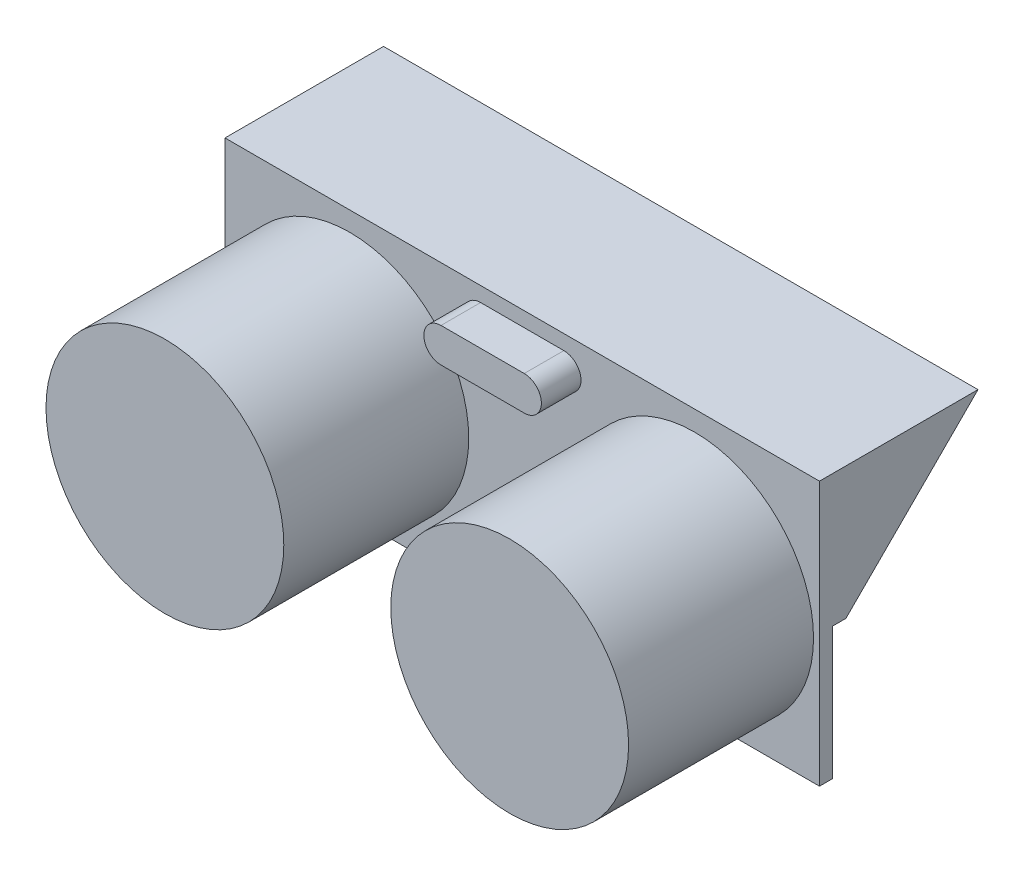
SolidWorks part; units mm, degrees
ref_plane "Plan de face" through (0, 0, 0) normal (0, 0, 1) x (1, 0, 0)
ref_plane "Plan de dessus" through (0, 0, 0) normal (0, 1, 0) x (1, 0, 0)
ref_plane "Plan de droite" through (0, 0, 0) normal (1, 0, 0) x (0, 0, -1)
sketch "Esquisse1" plane through (0, 0, 0) normal (0, 0, 1) x (1, 0, 0)
  line L1 (17.722, -4.0802) -> (-27.278, -4.0802)
  line L2 (17.722, -4.0802) -> (17.722, 15.9198)
  line L3 (17.722, 15.9198) -> (-27.278, 15.9198)
  line L4 (-27.278, -4.0802) -> (-27.278, 15.9198)
  dimension "D1" = 45
  dimension "D2" = 20
extrude "Boss.-Extru.1" add sketch "Esquisse1" along normal blind 1 contours L2 L1 L4 L3
sketch "Esquisse2" plane through (0, 0, 1) normal (0, 0, 1) x (1, 0, 0)
  line L0 (-27.278, -4.0802) -> (-27.278, 15.9198) construction
  line L1 (17.722, -4.0802) -> (17.722, 15.9198) construction
  circle A0 centre (-17.828, 5.4565) radius 9
  circle A1 centre (8.272, 5.4101) radius 9
  dimension "D1" = 18
  dimension "D2" = 18
  dimension "D3" = 9.45
  dimension "D4" = 9.45
extrude "Boss.-Extru.3" add sketch "Esquisse2" along normal blind 14 contours A1 | A0
sketch "Esquisse3" plane through (0, 0, 1) normal (0, 0, 1) x (1, 0, 0)
  line L1 (-7.9288, 14.8025) -> (-1.6273, 14.8025)
  line L3 (-7.9288, 12.2077) -> (-1.6273, 12.2077)
  arc A0 (-7.9288, 14.8025) -> (-7.9288, 12.2077) centre (-7.9288, 13.5051) ccw
  arc A1 (-1.6273, 12.2077) -> (-1.6273, 14.8025) centre (-1.6273, 13.5051) ccw
extrude "Boss.-Extru.4" add sketch "Esquisse3" along normal blind 3 contours L1 A1 L3 A0
sketch "Esquisse4" plane through (0.9463, -1.2088, 0) normal (0, 0, -1) x (-1, 0, 0)
  line L0 (28.2243, -2.8714) -> (28.2243, 17.1286) construction
  line L1 (2.5728, 0.425) -> (8.8743, 0.425)
  line L3 (2.5728, -2.1678) -> (8.8743, -2.1678)
  line L4 (-16.7757, -2.8714) -> (28.2243, -2.8714) construction
  arc A0 (2.5728, 0.425) -> (2.5728, -2.1678) centre (2.5728, -0.8714) ccw
  arc A1 (8.8743, -2.1678) -> (8.8743, 0.425) centre (8.8743, -0.8714) ccw
  dimension "D1" = 19.35
  dimension "D2" = 2
extrude "Boss.-Extru.5" add sketch "Esquisse4" along normal blind 6 and the other way blind 1.5 contours L1 A1 L3 A0
sketch "Sketch3" plane through (0, 0, 0) normal (0, 0, -1) x (-1, 0, 0)
  line L0 (27.278, -4.0802) -> (27.278, 15.9198) construction
  line L1 (-17.722, 15.9198) -> (27.278, 15.9198)
  line L2 (-17.722, 15.9198) -> (-17.722, 5.9198)
  line L3 (-17.722, 5.9198) -> (27.278, 5.9198)
  line L4 (27.278, 15.9198) -> (27.278, 5.9198)
  dimension "D1" = 10
extrude "Boss-Extrude1" add sketch "Sketch3" along normal blind 12
chamfer "Chamfer1" distance 11 angle 45 1 edges at (-4.778, 5.9198, -12)
